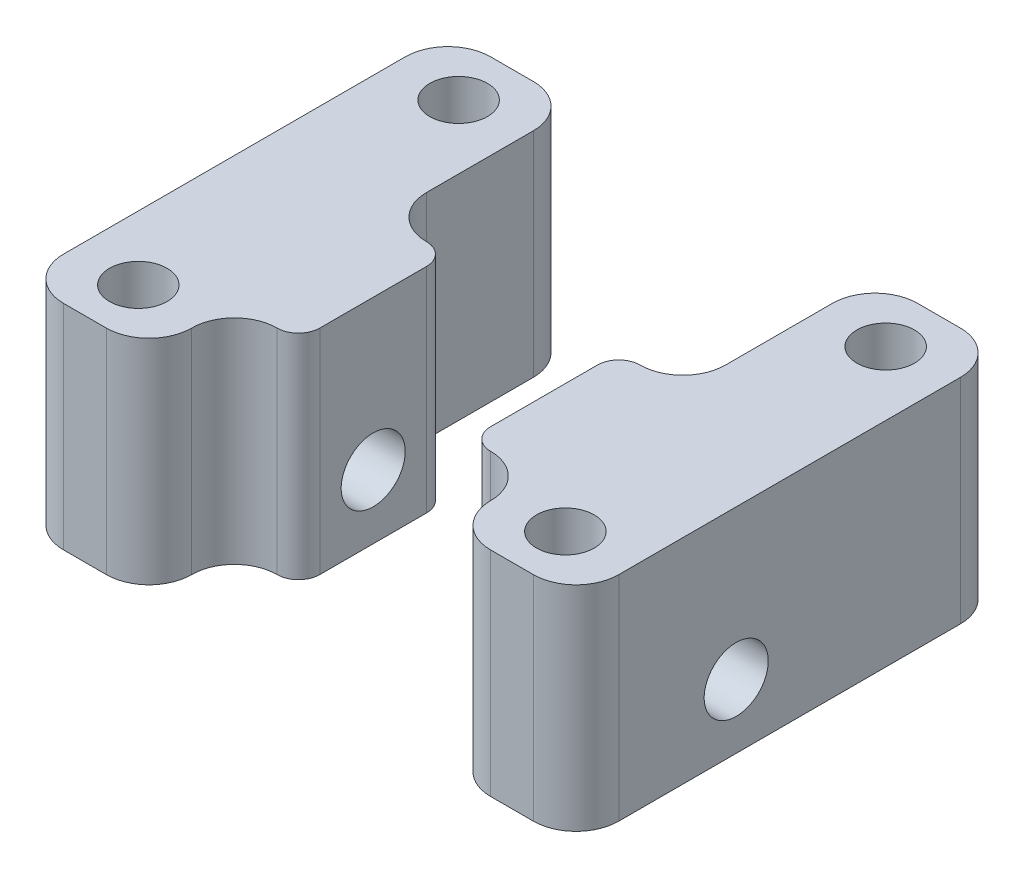
SolidWorks part; units mm, degrees
material "PLA"
ref_plane "前视基准面" through (0, 0, 0) normal (0, 0, 1) x (1, 0, 0)
ref_plane "上视基准面" through (0, 0, 0) normal (0, 1, 0) x (1, 0, 0)
ref_plane "右视基准面" through (0, 0, 0) normal (1, 0, 0) x (0, 0, -1)
sketch "草图1" plane through (0, 0, 0) normal (0, 1, 0) x (1, 0, 0)
  line L1 (-13, -10) -> (13, -10)
  line L2 (-13, -10) -> (-13, 10)
  line L3 (-13, 10) -> (13, 10)
  line L4 (13, -10) -> (13, 10)
  line L5 (0, 10) -> (0, -10) construction
  line L6 (-13, 0) -> (13, 0) construction
  circle A0 centre (-10, 7.5) radius 1.35
  circle A1 centre (10, 7.5) radius 1.35
  circle A2 centre (10, -7.5) radius 1.35
  circle A3 centre (-10, -7.5) radius 1.35
  point P0 (0, 0)
  dimension "D5" = 2.7
  dimension "D1" = 15
  dimension "D2" = 3
  dimension "D3" = 26
  dimension "D4" = 20
extrude "凸台-拉伸1" add sketch "草图1" along normal blind 10
sketch "草图2" plane through (0, 10, 0) normal (0, 1, 0) x (1, 0, 0)
  line L0 (-13, -10) -> (13, -10) construction
  line L1 (7, 10) -> (-7, 10)
  line L2 (7, 10) -> (7, -10)
  line L3 (7, -10) -> (-7, -10)
  line L4 (-7, 10) -> (-7, -10)
  line L5 (0, -10) -> (0, 10) construction
  line L6 (7, 0) -> (-7, 0) construction
  line L7 (-13, 10) -> (-13, -10) construction
  point P0 (0, 0)
  dimension "D1" = 6
extrude "切除-拉伸1" cut sketch "草图2" against normal through all
sketch "草图6" plane through (0, 0, 0) normal (0, -1, 0) x (1, 0, 0)
  line L0 (-7, -10) -> (-7, 10) construction
  line L1 (-7, 6) -> (-4, 6)
  line L2 (-7, 6) -> (-7, -1)
  line L3 (-7, -1) -> (-4, -1)
  line L4 (-4, 6) -> (-4, -1)
  line L5 (-5.5, -1) -> (-5.5, 6) construction
  line L6 (-7, 2.5) -> (-4, 2.5) construction
  line L7 (-7, -10) -> (-13, -10) construction
  line L8 (0, 0) -> (0, -3.7807) construction
  line L9 (7, -1) -> (4, -1)
  line L10 (4, 6) -> (4, -1)
  line L11 (7, 6) -> (4, 6)
  line L12 (7, 6) -> (7, -1)
  point P172 (-5.5, 2.5)
  dimension "D1" = 12.5
  dimension "D2" = 8
  dimension "D3" = 3
  dimension "D4" = 7
extrude "凸台-拉伸2" add sketch "草图6" against normal up to surface (10 mm away) up to face at (-10, 10, 6.15)
sketch "草图5" plane through (13, 0, 0) normal (1, 0, 0) x (0, 0, -1)
  line L0 (-10, 10) -> (10, 10) construction
  line L1 (10, 10) -> (10, 0) construction
  circle A0 centre (-2.5, 3) radius 1.5
  dimension "D2" = 3
  dimension "D1" = 12.5
  dimension "D3" = 7
extrude "切除-拉伸2" cut sketch "草图5" against normal through all
fillet "圆角1" radius 2 6 edges at (13, 5, 10) (13, 5, -10) (7, 5, -10) (7, 5, 10) (7, 5, -1) (7, 5, 6)
fillet "圆角2" radius 2 6 edges at (-13, 5, -10) (-7, 5, -10) (-7, 5, 10) (-13, 5, 10) (-7, 5, -1) (-7, 5, 6)
fillet "圆角3" radius 1 2 edges at (4, 5, -1) (4, 5, 6)
fillet "圆角4" radius 1 2 edges at (-4, 5, -1) (-4, 5, 6)
move or copy body "实体-移动/复制1" [suppressed] bodies to move or copy 109 110
